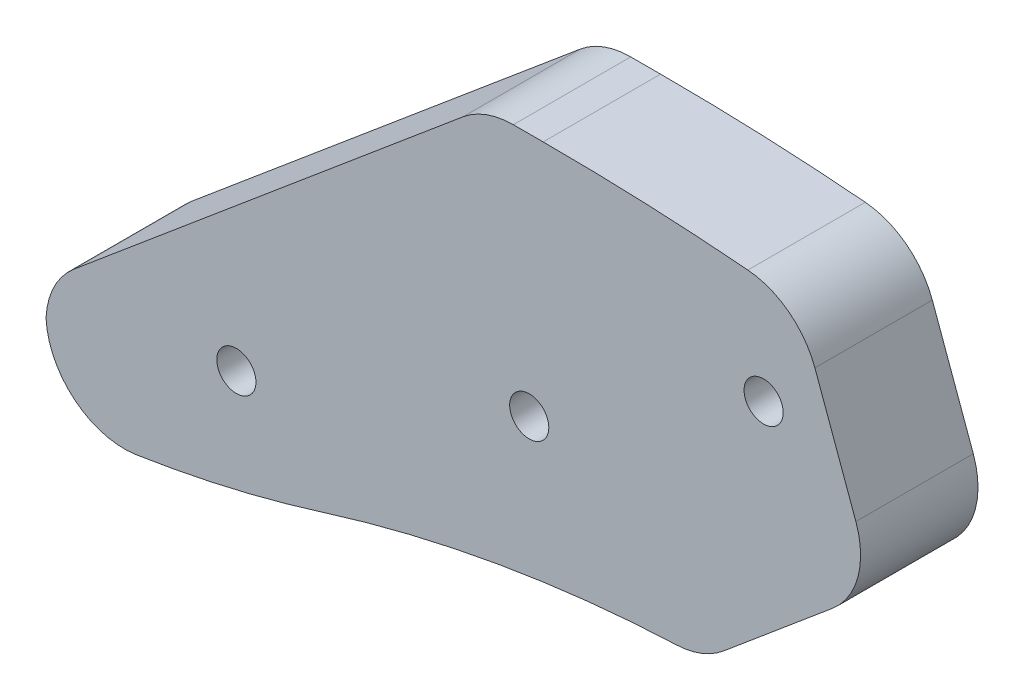
SolidWorks part; units mm, degrees
ref_plane "Front Plane" through (0, 0, 0) normal (0, 0, 1) x (1, 0, 0)
ref_plane "Top Plane" through (0, 0, 0) normal (0, 1, 0) x (1, 0, 0)
ref_plane "Right Plane" through (0, 0, 0) normal (1, 0, 0) x (0, 0, -1)
sketch "Sketch1" plane through (0, 0, 0) normal (0, 0, 1) x (1, 0, 0)
  line L0 (0, 0) -> (120, 0) construction
  line L1 (0, 25) -> (61.4231, 25)
  line L2 (0, 0) -> (0, -25) construction
  line L3 (120, 0) -> (31.8574, -73.9605) construction
  line L4 (0, 0) -> (74.5287, 62.537) construction
  line L5 (10.606, -12.6397) -> (55.4633, 25)
  line L6 (0, -16.5) -> (16.449, -16.5) construction
  line L7 (10.606, -12.6397) -> (10.606, -24.5666)
  line L8 (108.7512, 13.4058) -> (20.4598, -60.6795)
  line L9 (95.2972, 2.1165) -> (87.4633, 23.6401)
  circle A0 centre (0, 0) radius 25
  circle A1 centre (120, 0) radius 17.5
  arc A2 (61.4231, 25) -> (124.409, 16.9355) centre (61.4231, -225) cw
  arc A3 (38.9734, -19.0205) -> (0, -25) centre (0, 105) cw
  arc A4 (38.9734, -19.0205) -> (115.6605, -16.9534) centre (80.9448, -152.5809) cw
  circle A5 centre (0, 0) radius 16.5
  circle A6 centre (0, 0) radius 11.5 construction
  dimension "D1" = 50
  dimension "D3" = 35
  dimension "D4" = 250
  dimension "D5" = 130
  dimension "D6" = 140
  dimension "D7" = 33
  dimension "D9" = 23
  dimension "D2" = 120
  dimension "D8" = 40
  dimension "D10" = 32
  dimension "D11" = 70
extrude "Boss-Extrude1" add sketch "Sketch1" along normal blind 12
sketch "Sketch4" plane through (0, 0, 12) normal (0, 0, 1) x (1, 0, 0)
  line L0 (0, 0) -> (30.0702, -10.9446) construction
  line L1 (0, 0) -> (60, 0) construction
  line L2 (0, 0) -> (83.9535, 13.2969) construction
  circle A4 centre (30.0702, -10.9446) radius 2
  circle A5 centre (83.9535, 13.2969) radius 2
  circle A8 centre (60, 0) radius 2
  dimension "D1" = 9
  dimension "D2" = 85
  dimension "D5" = 4
  dimension "D3" = 32
  dimension "D4" = 20
  dimension "D6" = 60
extrude "Cut-Extrude2" cut sketch "Sketch4" against normal through all
fillet "Fillet2" radius 8 6 edges at (77.7377, -12.6177, 6) (10.606, -24.5666, 6) (10.606, -12.6397, 6) (95.2972, 2.1165, 6) (87.4633, 23.6401, 6) (55.4633, 25, 6)
